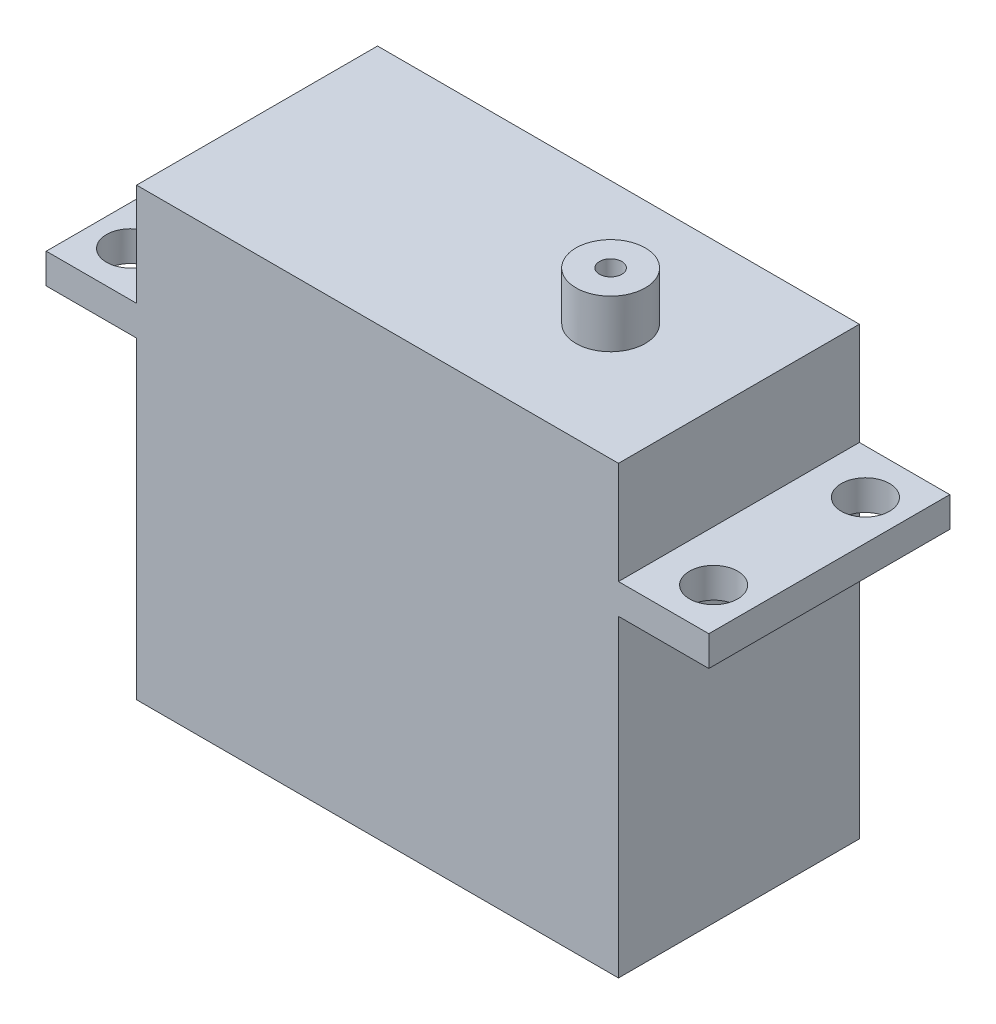
SolidWorks part; units mm, degrees
ref_plane "Front Plane" through (0, 0, 0) normal (0, 0, 1) x (1, 0, 0)
ref_plane "Top Plane" through (0, 0, 0) normal (0, 1, 0) x (1, 0, 0)
ref_plane "Right Plane" through (0, 0, 0) normal (1, 0, 0) x (0, 0, -1)
sketch "Sketch1" plane through (0, 0, 0) normal (0, 1, 0) x (1, 0, 0)
  line L1 (-20, -10) -> (20, -10)
  line L2 (-20, -10) -> (-20, 10)
  line L3 (-20, 10) -> (20, 10)
  line L4 (20, -10) -> (20, 10)
  line L5 (-20, -10) -> (20, 10) construction
  line L6 (-20, 10) -> (20, -10) construction
  point P0 (0, 0)
  dimension "D1" = 20
  dimension "D2" = 40
extrude "Body" add sketch "Sketch1" along normal blind 37
ref_plane "Plane1" through (0, 26, 0) normal (0, 1, 0) x (1, 0, 0)
sketch "Sketch2" plane through (0, 26, 0) normal (0, 1, 0) x (1, 0, 0)
  line L0 (-20, -10) -> (20, -10) construction
  line L1 (20, 10) -> (27.5, 10)
  line L2 (20, 10) -> (20, -10)
  line L3 (20, -10) -> (27.5, -10)
  line L4 (27.5, 10) -> (27.5, -10)
  line L5 (0, -14.3) -> (0, 14.3) construction
  line L6 (-20, -10) -> (-27.5, -10)
  line L7 (-27.5, 10) -> (-27.5, -10)
  line L8 (-20, 10) -> (-27.5, 10)
  line L9 (-20, 10) -> (-20, -10)
  dimension "D1" = 7.5
extrude "Flanges" add sketch "Sketch2" along normal blind 2.5
hole_wizard "Ø4.0 (4) Diameter Hole1" positions "Sketch3" profile "Sketch4" hole size "Ø4.0" standard "ANSI Metric" end condition through all
sketch "Sketch3" plane through (0, 28.5, 0) normal (0, 1, 0) x (1, 0, 0)
  line L1 (-24.2, 6.3) -> (24.2, 6.3) construction
  line L2 (-24.2, 6.3) -> (-24.2, -6.3) construction
  line L3 (-24.2, -6.3) -> (24.2, -6.3) construction
  line L4 (24.2, 6.3) -> (24.2, -6.3) construction
  line L5 (-27.5, 10) -> (-27.5, -10) construction
  line L6 (27.5, -10) -> (27.5, 10) construction
  line L7 (-27.5, 0) -> (27.5, 0) construction
  line L9 (-20, 10) -> (-27.5, 10) construction
  point P0 (-24.2, -6.3)
  point P2 (-24.2, 6.3)
  point P4 (24.2, 6.3)
  point P6 (24.2, -6.3)
  point P59 (-24.2, 0)
  dimension "D1" = 3.3
  dimension "D2" = 3.3
  dimension "D3" = 3.7
sketch "Sketch4" plane through (-24.2, 28.5, 6.3) normal (1, 0, 0) x (0, 0, 1)
  line L0 (0, 0) -> (0, 28.5)
  line L1 (0, 28.5) -> (2, 28.5)
  line L2 (2, 28.5) -> (2, 0)
  line L5 (2, 0) -> (0, 0)
  line L11 (0, -6.35) -> (0, 107.95) construction
  dimension "Thru Hole Dia." = 4
  dimension "Thru Hole Depth" = 28.5
sketch "Sketch5" plane through (0, 37, 0) normal (0, 1, 0) x (1, 0, 0)
  line L1 (-20, -10) -> (20, -10) construction
  line L2 (20, 10) -> (20, -10) construction
  circle A0 centre (9.625, -0.275) radius 2.875
  dimension "D1" = 5.75
  dimension "D2" = 9.725
  dimension "D3" = 10.375
extrude "Axle" add sketch "Sketch5" along normal blind 4
hole_wizard "Ø1.85 (1.85) Diameter Hole1" positions "Sketch6" profile "Sketch7" hole size "Ø1.85" standard "ANSI Metric"
sketch "Sketch6" plane through (0, 41, 0) normal (0, 1, 0) x (1, 0, 0)
  line L0 (9.625, 2.6) -> (9.625, -3.15) construction
  line L2 (6.75, -0.275) -> (12.5, -0.275) construction
  circle A0 centre (9.625, -0.275) radius 2.875 construction
  circle A1 centre (9.625, -0.275) radius 2.875 construction
  point P0 (9.625, -0.275)
  point P16 (9.625, -0.275)
sketch "Sketch7" plane through (9.625, 41, 0.275) normal (1, 0, 0) x (0, 0, 1)
  line L0 (0, 0) -> (0, 4.5558)
  line L1 (0, 4.5558) -> (0.925, 4)
  line L2 (0.925, 4) -> (0.925, 0)
  line L5 (0.925, 0) -> (0, 0)
  line L10 (0, 4.5558) -> (-0.925, 4) construction
  line L11 (0, -6.35) -> (0, 107.95) construction
  dimension "Hole Dia." = 1.85
  dimension "Hole Depth" = 4
  dimension "Drill Angle" = 118
equation "\"D1@Sketch2\"=(55-40)/2"
equation "\"D1@Sketch3\"=1.3 + 2"
equation "\"D2@Sketch3\"=\"D1@Sketch3\""
equation "\"D3@Sketch3\"= 1.7 + 2"
equation "\"D2@Sketch5\"=(\"D1@Sketch5\"/2) + 6.85"
equation "\"D3@Sketch5\"=(\"D1@Sketch5\"/2) + 7.5"
equation "\"D1@Axle\"=41-37mm"
